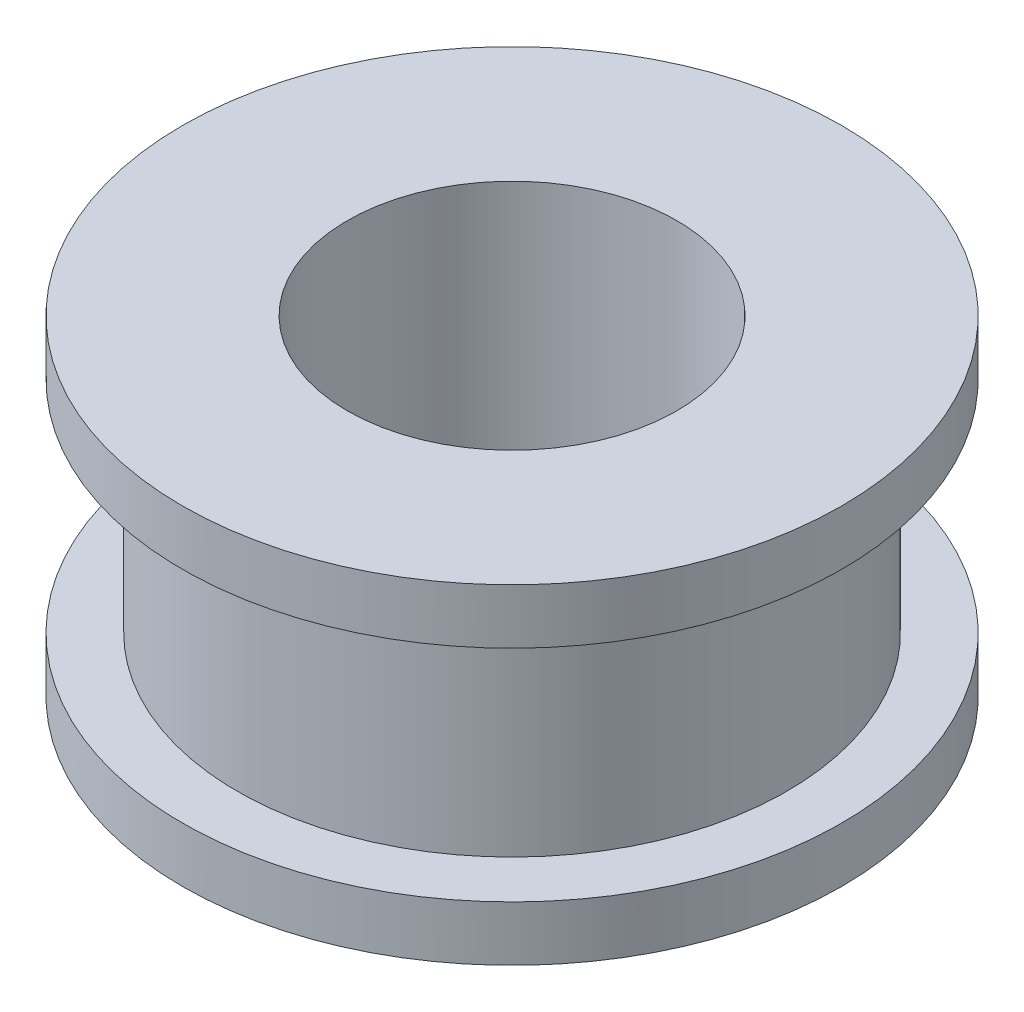
SolidWorks part; units mm, degrees
ref_plane "Front Plane" through (0, 0, 0) normal (0, 0, 1) x (1, 0, 0)
ref_plane "Top Plane" through (0, 0, 0) normal (0, 1, 0) x (1, 0, 0)
ref_plane "Right Plane" through (0, 0, 0) normal (1, 0, 0) x (0, 0, -1)
sketch "Sketch1" plane through (0, 0, 0) normal (0, 1, 0) x (1, 0, 0)
  circle A0 centre (0, 0) radius 6
  circle A1 centre (0, 0) radius 3
  dimension "D1" = 12
  dimension "D2" = 6
extrude "Boss-Extrude1" add sketch "Sketch1" along normal blind 6
sketch "Sketch2" plane through (0, 0, 0) normal (1, 0, 0) x (0, 0, -1)
  line L0 (6, 0) -> (5, 0) construction
  line L1 (-6, 0) -> (6, 0) construction
  line L2 (5, 0) -> (5, 1) construction
  line L3 (6, 1) -> (5, 1)
  line L4 (6, 0) -> (6, 6) construction
  line L5 (5, 1) -> (5, 5)
  line L6 (5, 5) -> (6, 5)
  line L7 (6, 5) -> (6, 1)
  line L8 (0, 0) -> (0, 6) construction
  line L9 (3, 6) -> (-3, 6) construction
  dimension "D1" = 1
  dimension "D2" = 1
  dimension "D3" = 4
revolve "Cut-Revolve1" cut sketch "Sketch2" angle 360 about L8
